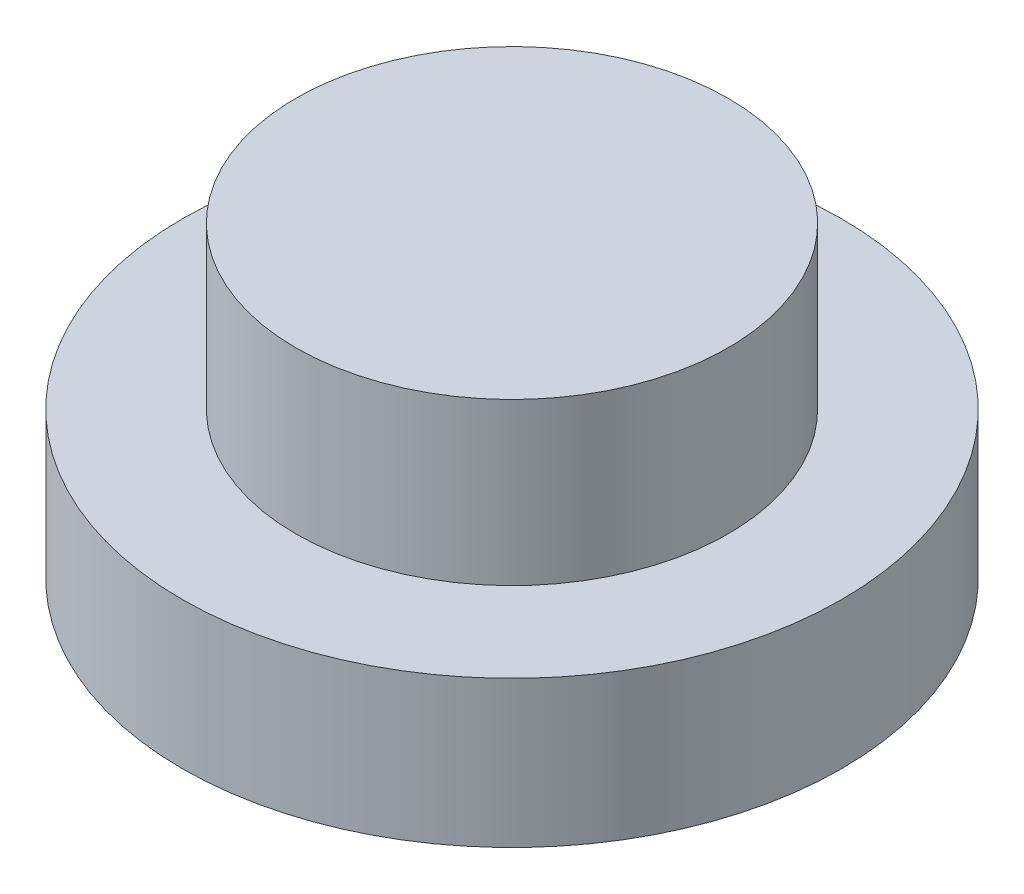
SolidWorks part; units mm, degrees
material "PTFE (general)"
ref_plane "Front Plane" through (0, 0, 0) normal (0, 0, 1) x (1, 0, 0)
ref_plane "Top Plane" through (0, 0, 0) normal (0, 1, 0) x (1, 0, 0)
ref_plane "Right Plane" through (0, 0, 0) normal (1, 0, 0) x (0, 0, -1)
sketch "Sketch1" plane through (0, 0, 0) normal (0, 1, 0) x (1, 0, 0)
  circle A0 centre (0, 0) radius 9
  dimension "D1" = 18
extrude "Boss-Extrude1" add sketch "Sketch1" along normal blind 4
sketch "Sketch2" plane through (0, 4, 0) normal (0, 1, 0) x (1, 0, 0)
  circle A0 centre (0, 0) radius 5.9
  dimension "D1" = 11.8
extrude "Boss-Extrude2" add sketch "Sketch2" along normal blind 20
sketch "Sketch5" plane through (0, 24, 0) normal (0, 1, 0) x (1, 0, 0)
  circle A0 centre (0, 0) radius 9.8378
extrude "Cut-Extrude3" cut sketch "Sketch5" against normal offset from surface (15.6 mm away) 4.4 up to face at (0, 4, 5.9)
